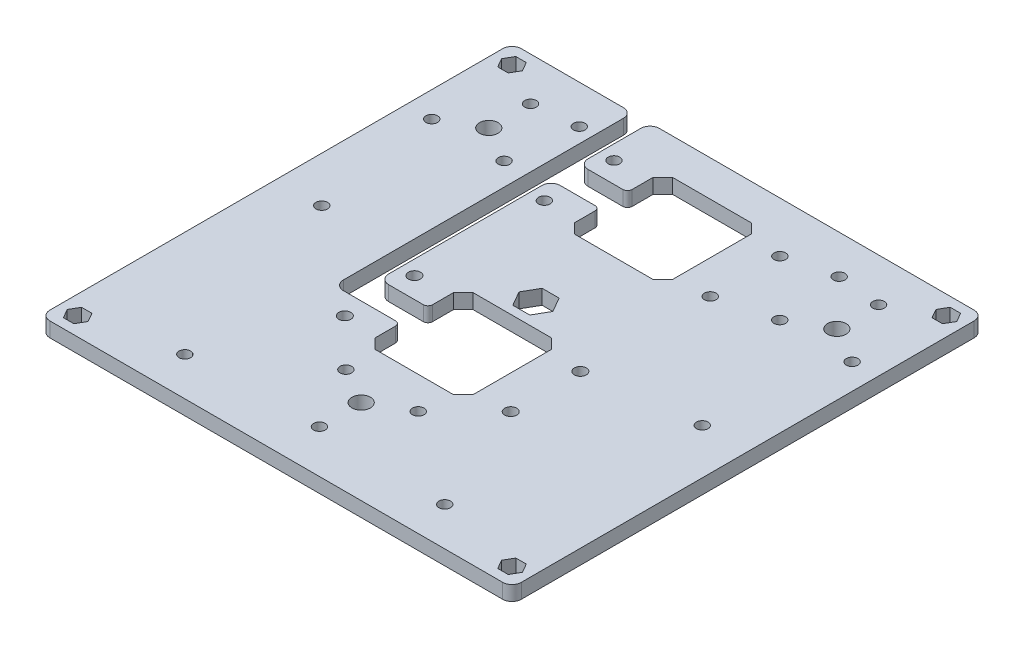
SolidWorks part; units mm, degrees
ref_plane "Plan de face" through (0, 0, 0) normal (0, 0, 1) x (1, 0, 0)
ref_plane "Plan de dessus" through (0, 0, 0) normal (0, 1, 0) x (1, 0, 0)
ref_plane "Plan de droite" through (0, 0, 0) normal (1, 0, 0) x (0, 0, -1)
sketch "Esquisse1" plane through (0, 0, 0) normal (0, 1, 0) x (1, 0, 0)
  line L1 (-101.6, -101.6) -> (101.6, -101.6)
  line L2 (-101.6, -101.6) -> (-101.6, 101.6)
  line L3 (-101.6, 101.6) -> (101.6, 101.6)
  line L4 (101.6, -101.6) -> (101.6, 101.6)
  line L5 (-101.6, -101.6) -> (101.6, 101.6) construction
  line L6 (-101.6, 101.6) -> (101.6, -101.6) construction
  point P0 (0, 0)
  dimension "D1" = 203.2
extrude "Boss.-Extru.1" add sketch "Esquisse1" along normal blind 6.35
sketch "Esquisse2" plane through (0, 6.35, 0) normal (0, 1, 0) x (1, 0, 0)
  circle A0 centre (-75, 65) radius 4
  circle A1 centre (75, 65) radius 4
  circle A2 centre (0, -65) radius 4
  dimension "D1" = 8
  dimension "D2" = 65
  dimension "D3" = 65
  dimension "D4" = 150
  dimension "D5" = 75
extrude "Enlèv. mat.-Extru.1" cut sketch "Esquisse2" against normal through all
sketch "Esquisse3" plane through (0, 6.35, 0) normal (0, 1, 0) x (1, 0, 0)
  line L0 (-16.9781, 86.15) -> (-21.15, 81.9781)
  line L1 (-21.15, 81.9781) -> (-21.15, 48.0219)
  line L2 (-21.15, 48.0219) -> (-16.9781, 43.85)
  line L3 (-16.9781, 43.85) -> (16.9781, 43.85)
  line L4 (16.9781, 43.85) -> (21.15, 48.0219)
  line L5 (21.15, 48.0219) -> (21.15, 81.9781)
  line L6 (21.15, 81.9781) -> (16.9781, 86.15)
  line L7 (16.9781, 86.15) -> (-16.9781, 86.15)
  line L9 (-75, 65) -> (75, 65) construction
  point P8 (0, 43.85)
  point P11 (0, 86.15)
  point P12 (-21.15, 65)
  point P13 (21.15, 65)
  dimension "D1" = 5.9
  dimension "D2" = 42.3
extrude "Enlèv. mat.-Extru.2" cut sketch "Esquisse3" against normal through all
sketch "Esquisse5" plane through (0, 6.35, 0) normal (0, 1, 0) x (1, 0, 0)
  circle A0 centre (-35.9, 49.85) radius 2.5
  circle A1 centre (-35.9, 79.85) radius 2.5
  circle A2 centre (35.6, 79.85) radius 2.5
  circle A3 centre (35.6, 49.85) radius 2.5
extrude "Enlèv. mat.-Extru.4" cut sketch "Esquisse5" against normal through all
sketch "Esquisse6" plane through (0, 6.35, 0) normal (0, 1, 0) x (1, 0, 0)
  circle A0 centre (93.6, -93.6) radius 2.5
  circle A1 centre (-93.6, -93.6) radius 2.5
  circle A2 centre (-93.6, 93.6) radius 2.5
  circle A3 centre (93.6, 93.6) radius 2.5
extrude "Enlèv. mat.-Extru.5" cut sketch "Esquisse6" against normal through all
sketch "Esquisse7" plane through (0, 6.35, 0) normal (0, 1, 0) x (1, 0, 0)
  line L0 (-97.6, -101.6) -> (97.6, -101.6) construction
  line L1 (-98.1033, -93.6) -> (-95.8517, -97.5)
  line L2 (-95.8517, -97.5) -> (-91.3483, -97.5)
  line L3 (-91.3483, -97.5) -> (-89.0967, -93.6)
  line L4 (-89.0967, -93.6) -> (-91.3483, -89.7)
  line L5 (-91.3483, -89.7) -> (-95.8517, -89.7)
  line L6 (-95.8517, -89.7) -> (-98.1033, -93.6)
  line L7 (89.0967, -93.6) -> (91.3483, -97.5)
  line L8 (91.3483, -97.5) -> (95.8517, -97.5)
  line L9 (95.8517, -97.5) -> (98.1033, -93.6)
  line L10 (98.1033, -93.6) -> (95.8517, -89.7)
  line L11 (95.8517, -89.7) -> (91.3483, -89.7)
  line L12 (91.3483, -89.7) -> (89.0967, -93.6)
  line L13 (89.0967, 93.6) -> (91.3483, 89.7)
  line L14 (91.3483, 89.7) -> (95.8517, 89.7)
  line L15 (95.8517, 89.7) -> (98.1033, 93.6)
  line L16 (98.1033, 93.6) -> (95.8517, 97.5)
  line L17 (95.8517, 97.5) -> (91.3483, 97.5)
  line L18 (91.3483, 97.5) -> (89.0967, 93.6)
  line L19 (-98.1033, 93.6) -> (-95.8517, 89.7)
  line L20 (-95.8517, 89.7) -> (-91.3483, 89.7)
  line L21 (-91.3483, 89.7) -> (-89.0967, 93.6)
  line L22 (-89.0967, 93.6) -> (-91.3483, 97.5)
  line L23 (-91.3483, 97.5) -> (-95.8517, 97.5)
  line L24 (-95.8517, 97.5) -> (-98.1033, 93.6)
  line L25 (97.6, 101.6) -> (-97.6, 101.6) construction
  circle A0 centre (-93.6, -93.6) radius 3.9 construction
  circle A1 centre (93.6, -93.6) radius 3.9 construction
  circle A2 centre (93.6, 93.6) radius 3.9 construction
  circle A3 centre (-93.6, 93.6) radius 3.9 construction
  dimension "D1" = 7.8
extrude "Enlèv. mat.-Extru.6" cut sketch "Esquisse7" against normal through all and the other way through all
sketch "Esquisse8" plane through (0, 6.35, 0) normal (0, 1, 0) x (1, 0, 0)
  circle A0 centre (90.5885, 56) radius 2.5
  circle A1 centre (59.4115, 56) radius 2.5
  circle A2 centre (75, 83) radius 2.5
  circle A3 centre (-90.5899, 55.9992) radius 2.5
  circle A4 centre (-75.0015, 82.9992) radius 2.5
  circle A5 centre (-59.413, 55.9992) radius 2.5
  circle A6 centre (-15.5885, -56) radius 2.5
  circle A7 centre (15.5885, -56) radius 2.5
  circle A8 centre (0, -83) radius 2.5
extrude "Enlèv. mat.-Extru.7" cut sketch "Esquisse8" against normal through all
sketch "Esquisse9" plane through (0, 6.35, 0) normal (0, 1, 0) x (1, 0, 0)
  line L0 (-101.6, -101.6) -> (101.6, -101.6) construction
  line L1 (-7.3035, 10.325) -> (-3.6517, 4)
  line L2 (-3.6517, 4) -> (3.6517, 4)
  line L3 (3.6517, 4) -> (7.3035, 10.325)
  line L4 (7.3035, 10.325) -> (3.6517, 16.65)
  line L5 (3.6517, 16.65) -> (-3.6517, 16.65)
  line L6 (-3.6517, 16.65) -> (-7.3035, 10.325)
  line L7 (3.6517, 16.65) -> (-3.6517, 16.65) construction
  line L8 (-7.3035, 10.325) -> (-3.6517, 4) construction
  circle A0 centre (0, 10.325) radius 6.325 construction
  dimension "D1" = 12.65
extrude "Enlèv. mat.-Extru.8" cut sketch "Esquisse9" against normal through all
sketch "Esquisse10" plane through (0, 0, 0) normal (0, -1, 0) x (1, 0, 0)
  circle A0 centre (56, -85) radius 2.5
  circle A1 centre (56, -85) radius 2.5 construction
  circle A2 centre (82, 0) radius 2.5
  circle A3 centre (82, 0) radius 2.5 construction
  circle A4 centre (56, 85) radius 2.5
  circle A5 centre (56, 85) radius 2.5 construction
extrude "Enlèv. mat.-Extru.9" cut sketch "Esquisse10" against normal through all
mirror "Symétrie1" about plane through (0, 0, 0) normal (1, 0, 0) of "Enlèv. mat.-Extru.9"
sketch "Esquisse13" plane through (0, 6.35, 0) normal (0, 1, 0) x (1, 0, 0)
  line L0 (16.9781, -42.15) -> (21.15, -37.9781)
  line L1 (21.15, -37.9781) -> (21.15, -4.0219)
  line L2 (21.15, -4.0219) -> (16.9781, 0.15)
  line L3 (16.9781, 0.15) -> (-16.9781, 0.15)
  line L4 (-16.9781, 0.15) -> (-21.15, -4.0219)
  line L5 (-21.15, -4.0219) -> (-21.15, -37.9781)
  line L6 (-21.15, -37.9781) -> (-16.9781, -42.15)
  line L7 (-16.9781, -42.15) -> (16.9781, -42.15)
  line L8 (16.9781, -42.15) -> (21.15, -37.9781) construction
  line L9 (21.15, -37.9781) -> (21.15, -4.0219) construction
  line L10 (-16.9781, -42.15) -> (16.9781, -42.15) construction
  line L11 (-21.15, -37.9781) -> (-16.9781, -42.15) construction
extrude "Enlèv. mat.-Extru.11" cut sketch "Esquisse13" against normal through all
sketch "Esquisse11" plane through (0, 6.35, 0) normal (0, 1, 0) x (1, 0, 0)
  line L0 (-21.15, 81.9781) -> (-21.15, 48.0219) construction
  line L1 (-21.15, 58.9281) -> (-42.1, 58.9281)
  line L2 (-21.15, 58.9281) -> (-21.15, 70.9281)
  line L3 (-21.15, 70.9281) -> (-42.1, 70.9281)
  line L5 (101.6, 101.6) -> (-101.6, 101.6) construction
  line L7 (-49.6, 58.9281) -> (-49.6, 101.6)
  line L8 (-49.6, 101.6) -> (-42.1, 101.6)
  line L9 (-42.1, 70.9281) -> (-42.1, 101.6)
  line L10 (-101.6, 101.6) -> (-101.6, -101.6) construction
  line L11 (-21.15, -4.0219) -> (-21.15, -37.9781) construction
  line L13 (-49.6, 58.9281) -> (-49.6, -15.0719)
  line L15 (-42.1, 58.9281) -> (-42.1, -15.0719)
  line L16 (-42.1, -15.0719) -> (-21.15, -15.0719)
  line L17 (-49.6, -15.0719) -> (-49.6, -27.0719)
  line L18 (-49.6, -27.0719) -> (-21.15, -27.0719)
  line L19 (-21.15, -15.0719) -> (-21.15, -27.0719)
  dimension "D1" = 7.5
  dimension "D2" = 12
  dimension "D3" = 11.05
  dimension "D4" = 52
  dimension "D5" = 11.05
extrude "Enlèv. mat.-Extru.10" cut sketch "Esquisse11" against normal through all
fillet "Congé1" radius 4 10 edges at (-42.1, 3.175, -101.6) (-49.6, 3.175, -101.6) (-42.1, 3.175, -70.9281) (-101.6, 3.175, 101.6) (101.6, 3.175, 101.6) (101.6, 3.175, -101.6) (-101.6, 3.175, -101.6) (-49.6, 3.175, 27.0719) (-42.1, 3.175, 15.0719) (-42.1, 3.175, -58.9281)
fillet "Congé2" radius 2 4 edges at (-21.15, 3.175, -58.9281) (-21.15, 3.175, -70.9281) (-21.15, 3.175, 27.0719) (-21.15, 3.175, 15.0719)
sketch "Esquisse16" plane through (0, 6.35, 0) normal (0, 1, 0) x (1, 0, 0)
  circle A0 centre (35.6, -36.15) radius 2.6
  circle A1 centre (35.6, -6.15) radius 2.6
  circle A2 centre (-35.9, -6.15) radius 2.6
  circle A3 centre (-35.9, -36.15) radius 2.6
  circle A4 centre (35.6, -36.15) radius 2.6 construction
extrude "Enlèv. mat.-Extru.12" cut sketch "Esquisse16" against normal through all
